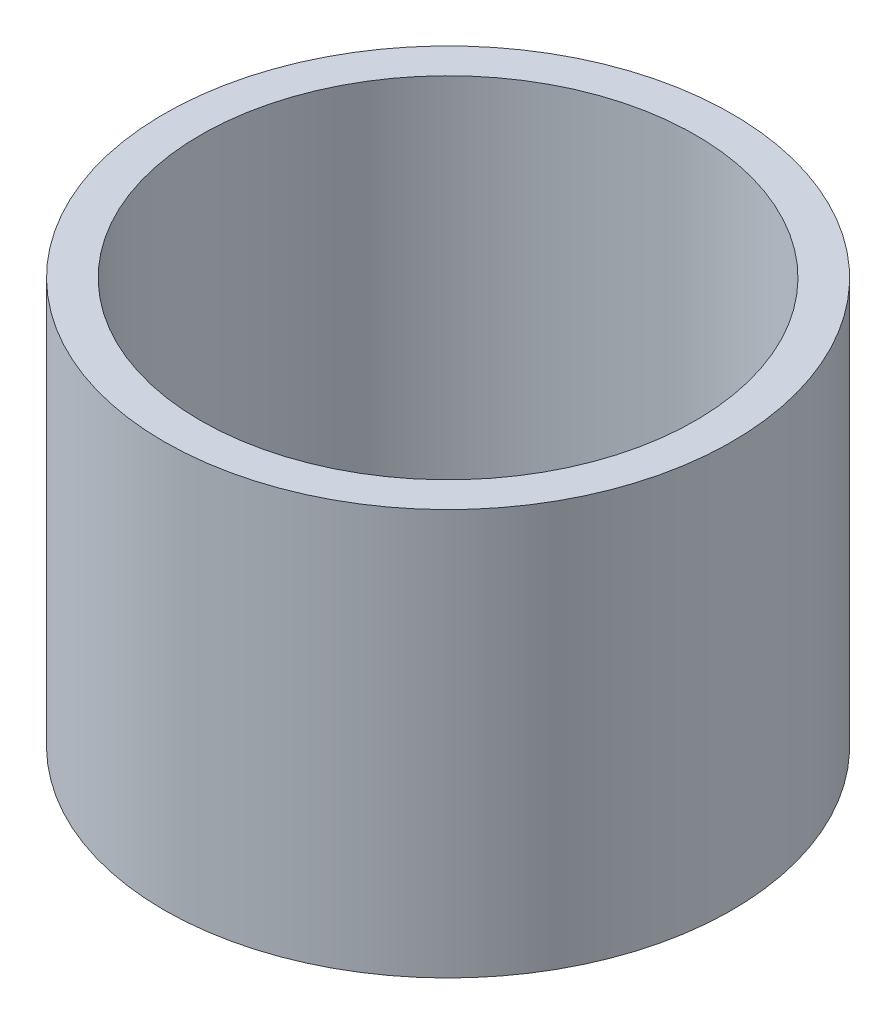
SolidWorks part; units mm, degrees
material "Brass"
ref_plane "Front Plane" through (0, 0, 0) normal (0, 0, 1) x (1, 0, 0)
ref_plane "Top Plane" through (0, 0, 0) normal (0, 1, 0) x (1, 0, 0)
ref_plane "Right Plane" through (0, 0, 0) normal (1, 0, 0) x (0, 0, -1)
sketch "Sketch1" plane through (0, 0, 0) normal (0, 1, 0) x (1, 0, 0)
  circle A0 centre (0, 0) radius 3.05
  circle A1 centre (0, 0) radius 3.5
  dimension "D1" = 7
  dimension "D2" = 6.1
extrude "Boss-Extrude1" add sketch "Sketch1" along normal blind 5
